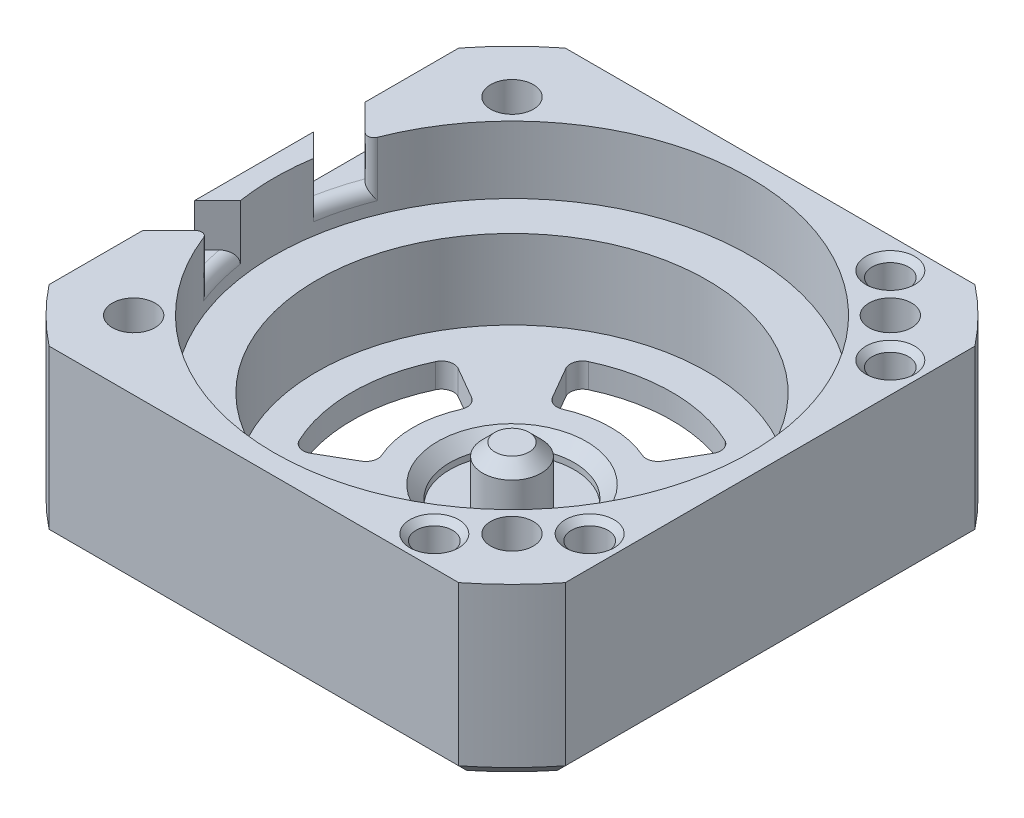
SolidWorks part; units mm, degrees
ref_plane "Front Plane" through (0, 0, 0) normal (0, 0, 1) x (1, 0, 0)
ref_plane "Top Plane" through (0, 0, 0) normal (0, 1, 0) x (1, 0, 0)
ref_plane "Right Plane" through (0, 0, 0) normal (1, 0, 0) x (0, 0, -1)
sketch "Sketch2" plane through (0, 0, 0) normal (0, 1, 0) x (1, 0, 0)
  line L1 (-21.15, 21.15) -> (21.15, 21.15)
  line L2 (-21.15, 21.15) -> (-21.15, -21.15)
  line L3 (-21.15, -21.15) -> (21.15, -21.15)
  line L4 (21.15, 21.15) -> (21.15, -21.15)
  line L5 (-21.15, 21.15) -> (21.15, -21.15) construction
  line L6 (-21.15, -21.15) -> (21.15, 21.15) construction
  point P0 (0, 0)
  dimension "D1" = 42.3
extrude "Boss-Extrude1" add sketch "Sketch2" along normal blind 14
sketch "Sketch3" plane through (0, 14, 0) normal (0, 1, 0) x (1, 0, 0)
  circle A0 centre (0, 0) radius 2.4
  dimension "D1" = 4.8
extrude "Cut-Extrude1" cut sketch "Sketch3" against normal through all
sketch "Sketch4" plane through (0, 14, 0) normal (0, 1, 0) x (1, 0, 0)
  line L1 (-15.5, 15.5) -> (15.5, 15.5) construction
  line L2 (-15.5, 15.5) -> (-15.5, -15.5) construction
  line L3 (-15.5, -15.5) -> (15.5, -15.5) construction
  line L4 (15.5, 15.5) -> (15.5, -15.5) construction
  line L5 (-15.5, 15.5) -> (15.5, -15.5) construction
  line L6 (-15.5, -15.5) -> (15.5, 15.5) construction
  circle A0 centre (-15.5, 15.5) radius 1.75
  circle A1 centre (15.5, 15.5) radius 1.75
  circle A2 centre (15.5, -15.5) radius 1.75
  circle A3 centre (-15.5, -15.5) radius 1.75
  point P0 (0, 0)
  point P16 (0, 0)
  dimension "D3" = 3.5
  dimension "D1" = 31
  dimension "D2" = 31
  dimension "D4" = 4
extrude "Cut-Extrude2" cut sketch "Sketch4" against normal through all
sketch "Sketch5" plane through (0, 14, 0) normal (0, 1, 0) x (1, 0, 0)
  circle A0 centre (0, 0) radius 27
  circle A1 centre (0, 0) radius 29.9106
  dimension "D1" = 54
extrude "Cut-Extrude4" cut sketch "Sketch5" against normal through all
sketch "Sketch6" plane through (0, 14, 0) normal (0, 1, 0) x (1, 0, 0)
  line L9 (-21.15, 4.8787) -> (-19.2683, 2.997)
  line L10 (-21.15, 9.1213) -> (-18.4221, 6.3934)
  line L11 (-16.7833, -21.15) -> (16.7833, -21.15) construction
  line L12 (6.4272, 21.15) -> (21.15, 6.4272) construction
  line L13 (7.3751, 21.15) -> (21.15, 7.3751) construction
  line L14 (16.7833, 21.15) -> (-16.7833, 21.15) construction
  line L15 (21.15, -16.7833) -> (21.15, 16.7833) construction
  line L18 (-21.15, 16.7833) -> (-21.15, -16.7833) construction
  line L24 (-21.15, 9.1213) -> (-21.15, 4.8787)
  line L25 (-21.15, -9.1213) -> (-18.4221, -6.3934)
  line L26 (-21.15, -4.8787) -> (-19.2683, -2.997)
  line L27 (-21.15, -4.8787) -> (-21.15, -9.1213)
  line L29 (-21.15, 7) -> (-21.15, -7) construction
  arc A0 (-18.4221, 6.3934) -> (-18.4221, -6.3934) centre (0, 0) cw
  arc A2 (-19.2683, 2.997) -> (-19.2683, -2.997) centre (0, 0) ccw
  circle A3 centre (0, 0) radius 11 construction
  circle A5 centre (15.5, 15.5) radius 1.75 construction
  arc A6 (-18.4221, -6.3934) -> (-18.4221, 6.3934) centre (0, 0) ccw
  dimension "D1" = 3
  dimension "D6" = 45
  dimension "D3" = 19.5
  dimension "D5" = 22
  dimension "D2" = 14
  dimension "D4" = 45
  dimension "D7" = 45
extrude "Cut-Extrude5" cut sketch "Sketch6" against normal offset from surface (12 mm away) 2
sketch "Sketch7" plane through (0, 2, 0) normal (0, 1, 0) x (1, 0, 0)
  circle A0 centre (0, 0) radius 5.1
  dimension "D1" = 10.2
extrude "Cut-Extrude6" cut sketch "Sketch7" against normal blind 1.5
sketch "Sketch8" plane through (0, 2, 0) normal (0, 1, 0) x (1, 0, 0)
  line L6 (-21.15, 4.8787) -> (-19.2683, 2.997)
  line L7 (-21.15, 4.8787) -> (-19.2683, 2.997)
  line L8 (-19.2683, -2.997) -> (-21.15, -4.8787)
  line L9 (-19.2683, -2.997) -> (-21.15, -4.8787)
  line L10 (-21.15, -4.8787) -> (-21.15, -9.1213)
  line L11 (-21.15, -4.8787) -> (-21.15, -9.1213)
  line L18 (-21.15, -9.1213) -> (-18.4221, -6.3934)
  line L20 (-21.15, -9.1213) -> (-18.4221, -6.3934)
  line L22 (-21.15, 9.1213) -> (-21.15, 4.8787)
  line L23 (-21.15, 9.1213) -> (-21.15, 4.8787)
  line L24 (-18.4221, 6.3934) -> (-21.15, 9.1213)
  line L25 (-18.4221, 6.3934) -> (-21.15, 9.1213)
  circle A0 centre (0, 0) radius 16
  arc A3 (-19.2683, 2.997) -> (-19.2683, -2.997) centre (0, 0) ccw
  arc A4 (-18.4221, -6.3934) -> (-18.4221, 6.3934) centre (0, 0) ccw
  arc A5 (-19.2683, 2.997) -> (-19.2683, -2.997) centre (0, 0) ccw
  arc A6 (-18.4221, -6.3934) -> (-18.4221, 6.3934) centre (0, 0) ccw
  dimension "D1" = 32
  dimension "D2" = 0
extrude "Boss-Extrude2" add sketch "Sketch8" along normal offset from surface (6.5 mm away) 5.5 up to face at (-15.5, 14, -13.75)
sketch "Sketch9" plane through (0, 14, 0) normal (0, 1, 0) x (1, 0, 0)
  line L0 (12.318, 18.682) -> (18.682, 12.318) construction
  line L1 (-16.7833, -21.15) -> (16.7833, -21.15) construction
  line L2 (-21.15, 0) -> (21.15, 0) construction
  line L3 (-21.15, 4.8787) -> (-21.15, -4.8787) construction
  line L4 (21.15, -16.7833) -> (21.15, 16.7833) construction
  line L5 (12.318, -18.682) -> (18.682, -12.318) construction
  circle A0 centre (15.5, 15.5) radius 1.75 construction
  circle A1 centre (12.318, 18.682) radius 1.5
  circle A2 centre (18.682, 12.318) radius 1.5
  circle A7 centre (18.682, -12.318) radius 1.5
  circle A8 centre (12.318, -18.682) radius 1.5
  point P2 (15.5, 15.5)
  dimension "D2" = 3
  dimension "D3" = 3
  dimension "D1" = 4.5
  dimension "D4" = 45
extrude "Cut-Extrude7" cut sketch "Sketch9" against normal blind 3
sketch "Sketch10" plane through (0, 8.5, 0) normal (0, 1, 0) x (1, 0, 0)
  line L1 (-18.4221, 6.3934) -> (-21.15, 9.1213)
  line L9 (-21.15, 9.1213) -> (-21.15, 4.8787)
  line L10 (-21.15, 4.8787) -> (-19.2683, 2.997)
  line L11 (-18.4221, -6.3934) -> (-21.15, -9.1213)
  line L12 (-21.15, -9.1213) -> (-21.15, -4.8787)
  line L13 (-21.15, -4.8787) -> (-19.2683, -2.997)
  arc A2 (-18.4221, 6.3934) -> (-19.2683, 2.997) centre (0, 0) ccw
  arc A3 (-18.4221, -6.3934) -> (-18.4221, 6.3934) centre (0, 0) ccw construction
  arc A4 (-19.2683, -2.997) -> (-18.4221, -6.3934) centre (0, 0) ccw
extrude "Boss-Extrude3" add sketch "Sketch10" along normal blind 2
chamfer "Chamfer1" distance 2 angle 45 4 edges at (15.5, 0, -13.75) (-15.5, 0, -13.75) (-15.5, 0, 17.25) (15.5, 0, 17.25)
chamfer "Chamfer3" distance 0.5 angle 45 4 edges at (12.318, 14, -17.182) (18.682, 14, -10.818) (18.682, 14, 10.818) (12.318, 14, 17.182)
chamfer "Chamfer4" distance 1 angle 45 8 edges at (19.0919, 0, 19.0919) (0, 0, 21.15) (-19.0919, 0, 19.0919) (-21.15, 0, 0) (-19.0919, 0, -19.0919) (0, 0, -21.15) (19.0919, 0, -19.0919) (21.15, 0, 0)
sketch "Sketch11" plane through (0, 2, 0) normal (0, 1, 0) x (1, 0, 0)
  line L0 (-6.55, 11.3449) -> (-4.05, 7.0148)
  line L1 (4.05, 7.0148) -> (6.55, 11.3449)
  line L2 (-21.15, 0) -> (21.15, 0) construction
  line L3 (-21.15, 4.8787) -> (-21.15, -4.8787) construction
  line L4 (21.15, -16.7833) -> (21.15, 16.7833) construction
  line L5 (11.3449, 6.55) -> (7.0148, 4.05)
  line L6 (7.0148, -4.05) -> (11.3449, -6.55)
  line L7 (6.55, -11.3449) -> (4.05, -7.0148)
  line L8 (-4.05, -7.0148) -> (-6.55, -11.3449)
  line L9 (-11.3449, -6.55) -> (-7.0148, -4.05)
  line L10 (-7.0148, 4.05) -> (-11.3449, 6.55)
  arc A0 (-4.05, 7.0148) -> (4.05, 7.0148) centre (0, 0) cw
  arc A1 (6.55, 11.3449) -> (-6.55, 11.3449) centre (0, 0) ccw
  circle A2 centre (0, 0) radius 5.1 construction
  arc A3 (7.0148, 4.05) -> (7.0148, -4.05) centre (0, 0) cw
  arc A4 (11.3449, -6.55) -> (11.3449, 6.55) centre (0, 0) ccw
  arc A5 (4.05, -7.0148) -> (-4.05, -7.0148) centre (0, 0) cw
  arc A6 (-6.55, -11.3449) -> (6.55, -11.3449) centre (0, 0) ccw
  arc A7 (-7.0148, -4.05) -> (-7.0148, 4.05) centre (0, 0) cw
  arc A8 (-11.3449, 6.55) -> (-11.3449, -6.55) centre (0, 0) ccw
  point P29 (0, 0)
  dimension "D1" = 60
  dimension "D3" = 3
  dimension "D4" = 5
  dimension "D2" = 60
  dimension "D5" = 4
extrude "Cut-Extrude8" cut sketch "Sketch11" against normal through all
fillet "Fillet12" radius 1 16 edges at (4.05, 1, 7.0148) (6.55, 1, 11.3449) (-6.55, 1, 11.3449) (-4.05, 1, 7.0148) (7.0148, 1, 4.05) (11.3449, 1, -6.55) (11.3449, 1, 6.55) (7.0148, 1, -4.05) (4.05, 1, -7.0148) (-4.05, 1, -7.0148) (6.55, 1, -11.3449) (-6.55, 1, -11.3449) (-7.0148, 1, -4.05) (-7.0148, 1, 4.05) (-11.3449, 1, 6.55) (-11.3449, 1, -6.55)
sketch "Sketch12" plane through (0, 0, 0) normal (0, -1, 0) x (1, 0, 0)
  circle A0 centre (0, 0) radius 2.4 construction
  circle A1 centre (0, 0) radius 2.4
extrude "Boss-Extrude4" add sketch "Sketch12" against normal blind 5
chamfer "Chamfer6" distance 1 angle 45 1 edges at (0, 5, -2.4)
chamfer "Chamfer7" distance 1 angle 45 1 edges at (0, 2, 5.1)
fillet "Fillet13" radius 0.5 2 edges at (-18.4221, 12.25, 6.3934) (-18.4221, 12.25, -6.3934)
fillet "Fillet14" radius 1 2 edges at (-18.8247, 10.5, -5.0873) (-18.8247, 10.5, 5.0873)
